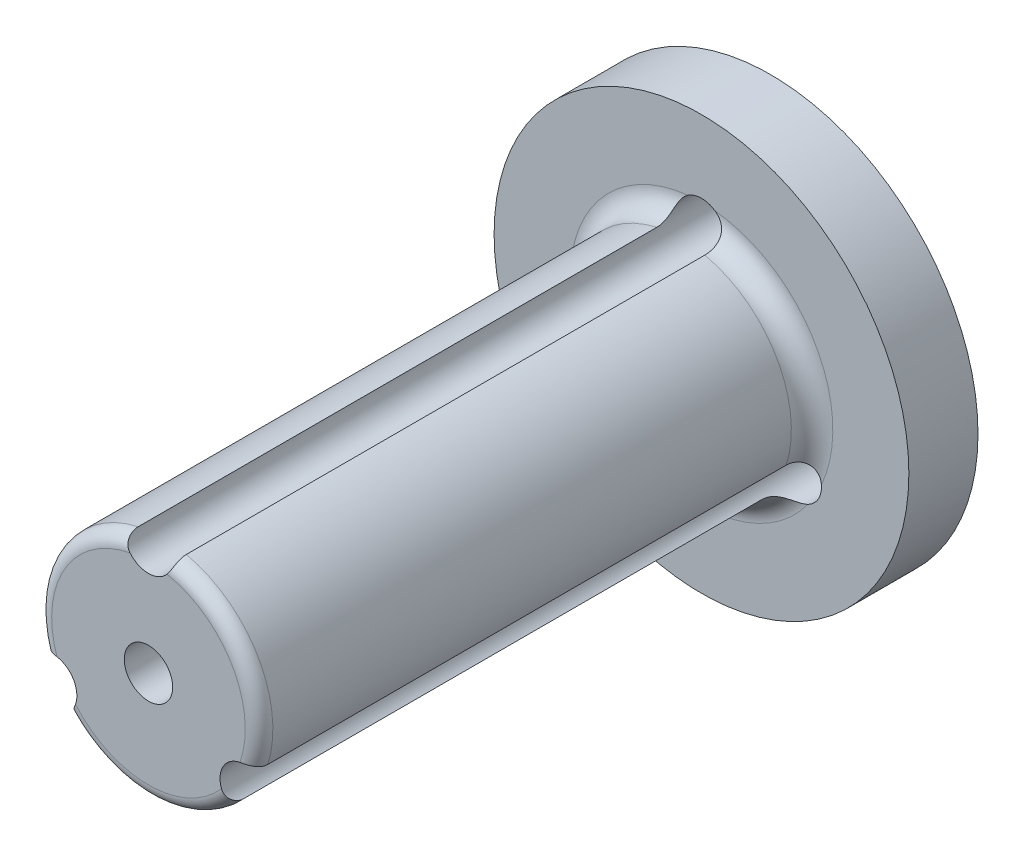
SolidWorks part; units mm, degrees
ref_plane "前视基准面" through (0, 0, 0) normal (0, 0, 1) x (1, 0, 0)
ref_plane "上视基准面" through (0, 0, 0) normal (0, 1, 0) x (1, 0, 0)
ref_plane "右视基准面" through (0, 0, 0) normal (1, 0, 0) x (0, 0, -1)
sketch "草图1" plane through (0, 0, 0) normal (0, 0, 1) x (1, 0, 0)
  circle A0 centre (0, 0) radius 15
  dimension "D1" = 30
extrude "凸台-拉伸1" add sketch "草图1" along normal blind 5
sketch "草图2" plane through (0, 0, 5) normal (0, 0, 1) x (1, 0, 0)
  circle A0 centre (0, 0) radius 8
  dimension "D1" = 16
extrude "凸台-拉伸2" add sketch "草图2" along normal blind 40
sketch "草图3" plane through (0, 0, 0) normal (0, 0, -1) x (-1, 0, 0)
  circle A0 centre (0, 0) radius 8 construction
  circle A1 centre (0, 8) radius 1.75
  circle A2 centre (0, 0) radius 1.75
  circle A3 centre (6.9282, -4) radius 1.75
  circle A4 centre (-6.9282, -4) radius 1.75
  dimension "D1" = 3.5
  dimension "D2" = 16
  dimension "D3" = 3.5
  dimension "D4" = 3
extrude "切除-拉伸1" cut sketch "草图3" against normal blind 49
fillet "圆角1" radius 1.5 3 edges at (6.9282, 4, 5) (0, -8, 5) (-6.9282, 4, 5)
fillet "圆角2" radius 1 3 edges at (6.9282, 4, 45) (0, -8, 45) (-6.9282, 4, 45)
